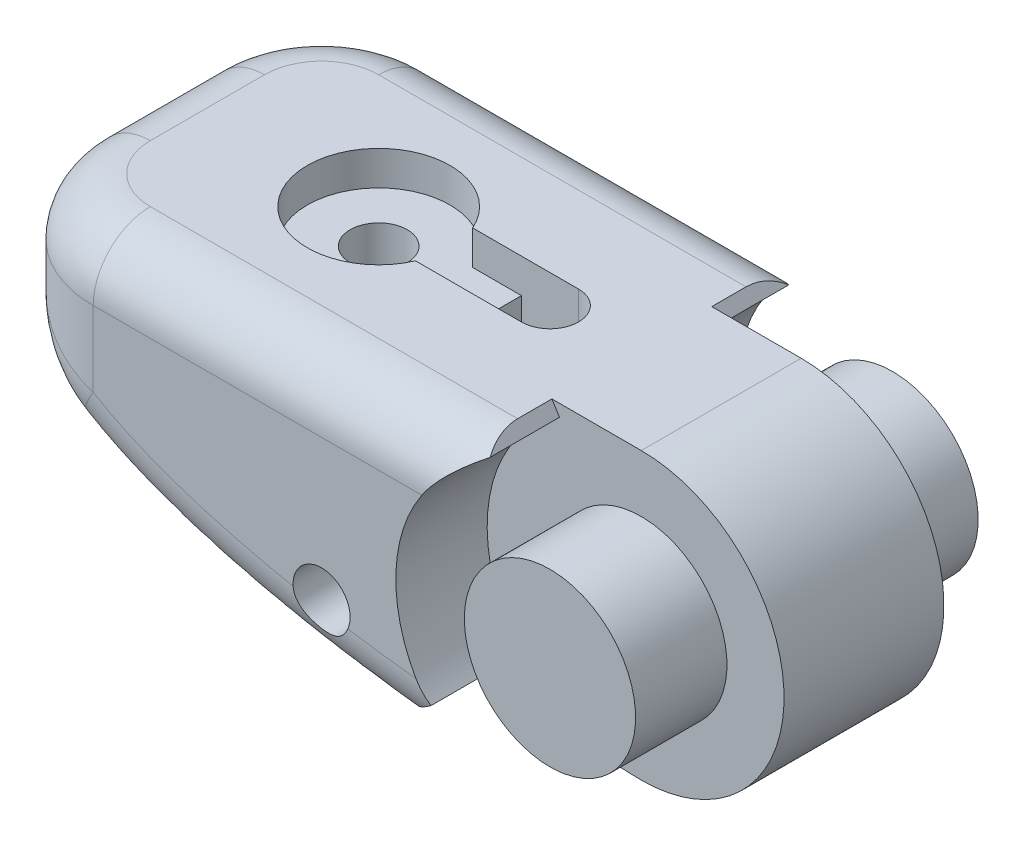
SolidWorks part; units mm, degrees
ref_plane "Front Plane" through (0, 0, 0) normal (0, 0, 1) x (1, 0, 0)
ref_plane "Top Plane" through (0, 0, 0) normal (0, 1, 0) x (1, 0, 0)
ref_plane "Right Plane" through (0, 0, 0) normal (1, 0, 0) x (0, 0, -1)
sketch "Width-Sketch" plane through (0, 0, 0) normal (0, 1, 0) x (1, 0, 0)
  line L0 (0, 0) -> (0, -2) construction
  line L1 (0, -2) -> (0, -4) construction
  line L2 (0, -4) -> (0, -6) construction
  line L3 (0, -6) -> (0, -8) construction
  line L4 (0, -8) -> (0, -10) construction
  dimension "D1" = 2
ref_plane "Centre-Plane" through (0, 0, 6) normal (0, 0, 1) x (1, 0, 0)
sketch "Sketch1" plane through (0, 0, 0) normal (0, 0, 1) x (1, 0, 0)
  line L0 (0, 5) -> (-20, 5)
  arc A2 (0, -5) -> (0, 5) centre (0, 0) ccw
  spline S0 degree 3 poles (-20, 5) (-22.8378, -4.4787) (-0.5767, -5.0045) (0, -5) knots 0 0 0 0 1 1 1 1
  dimension "D1" = 5
  dimension "D2" = 20
extrude "Boss-Extrude1" add sketch "Sketch1" along normal up to vertex (6 mm away) up to point (0, 0, 6)
surface "Surface-Offset1" parameters "D1"=0
sketch "Sketch15" plane through (0, 0, 0) normal (0, 0, -1) x (-1, 0, 0)
  line L0 (2.8667, 4.5763) -> (3.1321, 5)
  line L1 (0, 5) -> (20, 5) construction
  line L2 (3.1321, 5) -> (0.78, 5.3434)
  line L3 (5.8392, -4.5457) -> (4.261, -3.3172)
  line L4 (5.8392, -4.5457) -> (0.8414, -5.3341)
  arc A0 (4.261, -3.3172) -> (2.8667, 4.5763) centre (0, 0) ccw
  arc A1 (0, 5) -> (0, -5) centre (0, 0) ccw construction
  circle A2 centre (0, 0) radius 3
  arc A3 (0.78, 5.3434) -> (0.8414, -5.3341) centre (0, 0) ccw
  spline S0 degree 3 poles (20, 5) (22.8378, -4.4787) (0.5767, -5.0045) (0, -5) knots 0 0 0 0 1 1 1 1 construction
  dimension "D2" = 6
  dimension "D1" = 0.4
  dimension "D3" = 0.5
  dimension "D4" = 2
extrude "Cut-Extrude5" cut sketch "Sketch15" against normal blind 3.2
sketch "Sketch16" plane through (0, 0, 6) normal (0, 0, -1) x (-1, 0, 0)
  line L0 (7, 0) -> (5, 0)
  line L2 (7, 0) -> (7, -7)
  line L4 (0, -5) -> (0, -7)
  line L5 (0, -7) -> (7, -7)
  arc A1 (0, -5) -> (5, 0) centre (0, 0) ccw
  arc A2 (0, 5) -> (0, -5) centre (0, 0) ccw construction
  dimension "D1" = 2
  dimension "D2" = 2
extrude "Cut-Extrude6" cut sketch "Sketch16" along normal blind 1
sketch "Sketch17" plane through (0, 5, 0) normal (0, 1, 0) x (1, 0, 0)
  line L0 (0, -6) -> (-20, -6) construction
  line L1 (-7, -6) -> (-5, -6) construction
  line L2 (-7, -6) -> (-5, -6) construction
  line L3 (0, -6) -> (-20, -6) construction
  circle A0 centre (-6, -6) radius 1
  point P10 (-6, -6)
  dimension "D1" = 2
extrude "Cut-Extrude7" cut sketch "Sketch17" against normal through all
mirror "Mirror1" about plane through (0, 0, 6) normal (0, 0, 1) of bodies 117 111
sketch "Sketch18" plane through (0, 5, 0) normal (0, 1, 0) x (1, 0, 0)
  line L0 (-6, -5) -> (-9.7087, -5)
  line L1 (-6, -5) -> (-12, -5) construction
  line L2 (-6, -5) -> (-6, -7)
  line L3 (-6, -7) -> (-12, -7) construction
  line L4 (-12, -5) -> (-12, -7) construction
  line L6 (-9.7087, -7) -> (-6, -7)
  circle A0 centre (-6, -6) radius 1 construction
  circle A1 centre (-6, -6) radius 1 construction
  arc A2 (-9.7087, -5) -> (-9.7087, -7) centre (-12, -6) ccw
  dimension "D1" = 2.5
  dimension "D2" = 6
extrude "Cut-Extrude8" cut sketch "Sketch18" against normal blind 1.2
sketch "Sketch19" plane through (0, 3.8, 0) normal (0, 1, 0) x (1, 0, 0)
  circle A0 centre (-12, -6) radius 1
  arc A1 (-9.7087, -5) -> (-9.7087, -7) centre (-12, -6) ccw construction
  dimension "D1" = 2
extrude "Cut-Extrude9" cut sketch "Sketch19" against normal through all
sketch "Sketch20" plane through (0, 0, 6) normal (0, 0, 1) x (1, 0, 0)
  line L0 (-11, 3.8) -> (-13, 3.8) construction
  line L1 (-11, 3.8) -> (-13, 3.8) construction
  line L2 (-11, 3.8) -> (-11, -3.6248) construction
  line L3 (-13, 3.8) -> (-13, -3.0777) construction
  line L4 (-12, -6.9171) -> (-10.5, -6.9171)
  line L5 (-10.5, -6.9171) -> (-10.5, -1.1585)
  line L6 (-10.5, 2.2) -> (-12, 2.2)
  line L8 (-12, 3.8) -> (-12, -6.9171) construction
  line L9 (-12, -6.9171) -> (-12, 2.2)
  line L10 (-13, -3.0777) -> (-11, -3.0777) construction
  line L11 (-10.5, -2.9171) -> (-13.5, -2.9171) construction
  line L12 (-10.5, 0.4415) -> (-8.5, 0.4415)
  line L13 (-8.5, 0.4415) -> (-8.5, -1.1585)
  line L14 (-8.5, -1.1585) -> (-10.5, -1.1585)
  line L15 (-10.5, 0.4415) -> (-10.5, 2.2)
  line L16 (-11.3066, -2.9171) -> (-11.3066, 2.2) construction
  line L17 (-8.5, -0.3585) -> (-11.3066, -0.3585) construction
  line L18 (-9.7087, 3.8) -> (-14.5, 3.8) construction
  spline S0 degree 3 poles (933.554, 306.2072) (-1088.3019, -222.2646) (1085.3581, 146.3306) (-1000.2438, -110.138) knots -2.269073 -2.269073 -2.269073 -2.269073 3.384684 3.384684 3.384684 3.384684 only from (-20, 5) to (-5.8392, -4.5457) construction
  spline S1 degree 3 poles (-20, 5) (-21.9144, -1.3943) (-12.4066, -3.7143) (-5.8392, -4.5457) knots 0 0 0 0 0.674599 0.674599 0.674599 0.674599 construction
  point P15 (-12, -2.9171)
  dimension "D1" = 1.5
  dimension "D2" = 1.6
  dimension "D3" = 1.6
  dimension "D4" = 2
revolve "Cut-Revolve2" cut sketch "Sketch20" angle 360 about L9
sketch "Sketch21" plane through (0, 0.4415, 0) normal (0, -1, 0) x (1, 0, 0)
  line L0 (-7, 7) -> (-6, 7) construction
  line L1 (-8.6459, 7) -> (-6, 7)
  line L2 (-7, 5) -> (-6, 5) construction
  line L3 (-8.6459, 5) -> (-6, 5)
  line L4 (-6, 7) -> (-6, 5)
  circle A1 centre (-12, 6) radius 3.5
  arc A2 (-8.6459, 5) -> (-8.6459, 7) centre (-12, 6) ccw
  dimension "D1" = 0
extrude "Cut-Extrude10" cut sketch "Sketch21" along normal up to surface (1.6 mm away) up to face at (-12, -1.1585, 2.5)
sketch "Sketch22" plane through (0, 3.8, 0) normal (0, 1, 0) x (1, 0, 0)
  line L0 (-6, -5) -> (-9.7087, -5) construction
  line L1 (-8, -5) -> (-6, -5)
  line L2 (-8, -5) -> (-8, -7)
  line L3 (-8, -7) -> (-6, -7)
  line L4 (-6, -5) -> (-6, -7)
  line L5 (-7, -7) -> (-7, -5) construction
  line L6 (-7, -7) -> (-7, -5) construction
  dimension "D1" = 1
extrude "Cut-Extrude11" cut sketch "Sketch22" against normal through all both and the other way through all
sketch "Sketch23" plane through (0, 0, 5) normal (0, 0, 1) x (1, 0, 0)
  line L0 (-8, -4.2297) -> (-8, -1.1585) construction
  line L1 (-8, -1.9585) -> (-8, -1.1585) construction
  line L2 (-8, -1.1585) -> (-7.2, -1.1585) construction
  line L3 (-8, -4.2297) -> (-8, -1.1585) construction
  line L9 (-7.2, -1.1585) -> (-7.2, -1.9585) construction
  line L10 (-7.2, -1.9585) -> (-8, -1.9585) construction
  circle A0 centre (-8, -1.9585) radius 1
  dimension "D1" = 2
  dimension "D2" = 0.8
extrude "Cut-Extrude12" cut sketch "Sketch23" against normal through all both and the other way through all
sketch "Sketch24" plane through (0, 5, 0) normal (0, 1, 0) x (1, 0, 0)
  line L0 (-20, -8) -> (-20, -4)
  line L1 (-16, -12) -> (-28, -12)
  line L2 (-28, -12) -> (-28, 0)
  line L3 (-28, 0) -> (-16, 0)
  line L4 (-20, -12) -> (-20, 0) construction
  line L5 (-3.1321, 0) -> (-20, 0) construction
  line L6 (-3.1321, -12) -> (-20, -12) construction
  arc A0 (-20, -4) -> (-16, 0) centre (-16, -4) cw
  arc A1 (-20, -8) -> (-16, -12) centre (-16, -8) ccw
  dimension "D2" = 4
extrude "Cut-Extrude13" cut sketch "Sketch24" against normal through all
fillet "Fillet1" radius 2 10 edges at (-9.566, 5, 0) (-18.8284, 5, 1.1716) (-20, 5, 6) (-18.8284, 5, 10.8284) (-9.566, 5, 12) (-19.5827, 1.0305, 9.7788) (-20, 1.9071, 6) (-19.7539, 1.3359, 2.6185)
equation "\"Ligament\"=2"
equation "\"Clearance\"=0.4"
equation "\"D1@Sketch15\"=\"Clearance\""
equation "\"D1@Sketch17\"=\"Ligament\""
equation "\"D1@Sketch16\"=\"Ligament\""
equation "\"D1@Cut-Extrude6\"=\"Ligament\"/2"
equation "\"D1@Cut-Extrude8\"=\"Ligament\"/2"
equation "\"Trim\"=0.5"
equation "\"D3@Sketch15\"=\"Trim\""
equation "\"D4@Sketch15\"=\"Trim\"*4"
equation "\"D2@Sketch23\"=\"Clearance\"*2"
equation "\"D1@Width-Sketch\"   = \"Ligament\""
